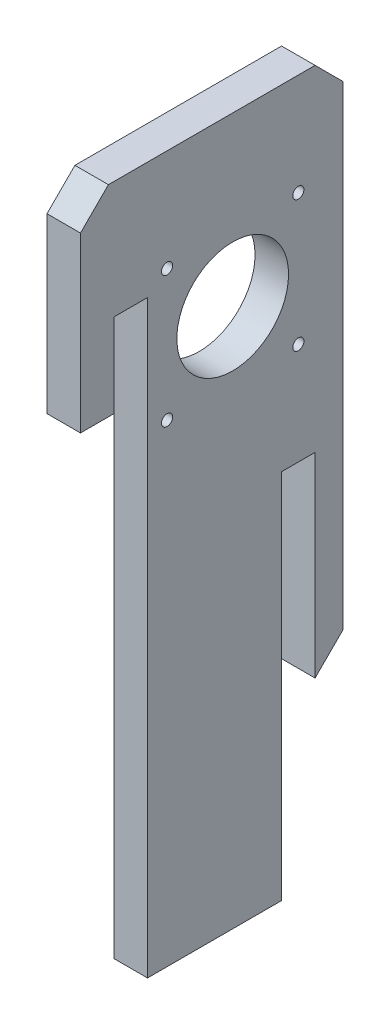
SolidWorks part; units mm, degrees
material "Beech"
ref_plane "Front Plane" through (0, 0, 0) normal (0, 0, 1) x (1, 0, 0)
ref_plane "Top Plane" through (0, 0, 0) normal (0, 1, 0) x (1, 0, 0)
ref_plane "Right Plane" through (0, 0, 0) normal (1, 0, 0) x (0, 0, -1)
sketch "Sketch1" plane through (0, 0, 0) normal (1, 0, 0) x (0, 0, -1)
  line L1 (-29.5, 60) -> (29.5, 60)
  line L2 (-29.5, 60) -> (-29.5, -60)
  line L3 (-29.5, -60) -> (29.5, -60)
  line L4 (29.5, 60) -> (29.5, -60)
  line L5 (-29.5, 60) -> (29.5, -60) construction
  line L6 (-29.5, -60) -> (29.5, 60) construction
  circle A0 centre (0, 0) radius 20
  point P0 (0, 0)
  dimension "D3" = 40
  dimension "D1" = 59
  dimension "D2" = 120
extrude "Boss-Extrude1" add sketch "Sketch1" along normal blind 12
hole_wizard "Ø4.0 (4) Diameter Hole1" positions "Sketch5" profile "Sketch4" hole size "Ø4.0" standard "ISO" end condition up to next
sketch "Sketch5" plane through (0, 0, 0) normal (-1, 0, 0) x (0, 0, 1)
  point P0 (-23.5, 23.5)
  point P1 (23.5, 23.5)
  point P3 (23.5, -23.5)
  point P5 (-23.5, -23.5)
  dimension "D1" = 23.5
  dimension "D2" = 23.5
  dimension "D3" = 23.5
  dimension "D4" = 23.5
  dimension "D5" = 23.5
  dimension "D6" = 23.5
  dimension "D7" = 23.5
  dimension "D8" = 23.5
sketch "Sketch4" plane through (0, 23.5, -23.5) normal (0, 1, 0) x (0, 0, 1)
  line L0 (0, 0) -> (0, 12)
  line L1 (0, 12) -> (2, 12)
  line L2 (2, 12) -> (2, 0)
  line L5 (2, 0) -> (0, 0)
  line L11 (0, -6.35) -> (0, 107.95) construction
  dimension "Thru Hole Dia." = 4
  dimension "Thru Hole Depth" = 12
hole_wizard "Hole1" positions "Sketch7" profile "Sketch6" legacy
sketch "Sketch7" plane through (0, 0, 0) normal (-1, 0, 0) x (0, 0, 1)
  line L0 (0, -57.2998) -> (0, 35.7294) construction
  point P0 (0, 45)
  point P1 (0, -45)
  dimension "D1" = 45
  dimension "D2" = 45
sketch "Sketch6" plane through (0, 45, 0) normal (0, 1, 0) x (0, 0, 1)
  line L0 (0, 0) -> (0, 6)
  line L1 (0, 6) -> (6, 6)
  line L2 (6, 6) -> (6, 0)
  line L5 (6, 0) -> (0, 0)
  line L11 (0, -6.35) -> (0, 107.95) construction
  dimension "Thru Hole Dia." = 12
  dimension "Thru Hole Depth" = 6
sketch "Sketch8" plane through (0, 0, 0) normal (-1, 0, 0) x (0, 0, 1)
  line L0 (29.5, 60) -> (29.5, -60)
  line L2 (42.5, 18) -> (42.5, -12)
  line L3 (42.5, -12) -> (54.5, -12)
  line L4 (54.5, -12) -> (54.5, 60)
  line L5 (54.5, 60) -> (29.5, 60)
  line L6 (-29.5, 60) -> (29.5, 60) construction
  line L9 (29.5, -60) -> (30.5, -60)
  line L11 (30.5, -60) -> (30.5, 18)
  line L12 (30.5, 18) -> (42.5, 18)
  dimension "D1" = 1
  dimension "D2" = 12
  dimension "D3" = 12
  dimension "D4" = 30
  dimension "D5" = 42
extrude "Boss-Extrude2" add sketch "Sketch8" against normal blind 12
sketch "Sketch9" plane through (0, 0, 0) normal (-1, 0, 0) x (0, 0, 1)
  line L0 (-29.5, -60) -> (-29.5, 60) construction
  line L1 (30.5, -60) -> (-17.5, -60)
  line L2 (30.5, -60) -> (30.5, -193)
  line L3 (30.5, -193) -> (-17.5, -193)
  line L4 (-17.5, -60) -> (-17.5, -193)
  dimension "D1" = 12
  dimension "D2" = 133
extrude "Boss-Extrude3" add sketch "Sketch9" against normal blind 12
sketch "Sketch11" plane through (12, 0, 0) normal (1, 0, 0) x (0, 0, -1)
  line L1 (29.5, 60) -> (39.5, 60)
  line L2 (29.5, 60) -> (29.5, -130)
  line L3 (29.5, -130) -> (39.5, -130)
  line L4 (39.5, 60) -> (39.5, -130)
  dimension "D1" = 10
  dimension "D2" = 190
extrude "Boss-Extrude4" add sketch "Sketch11" against normal blind 12
chamfer "Chamfer1" distance 10 angle 45 2 edges at (6, 60, -39.5) (6, 60, 54.5)
chamfer "Chamfer2" distance 10 angle 45 1 edges at (6, -130, -39.5)
